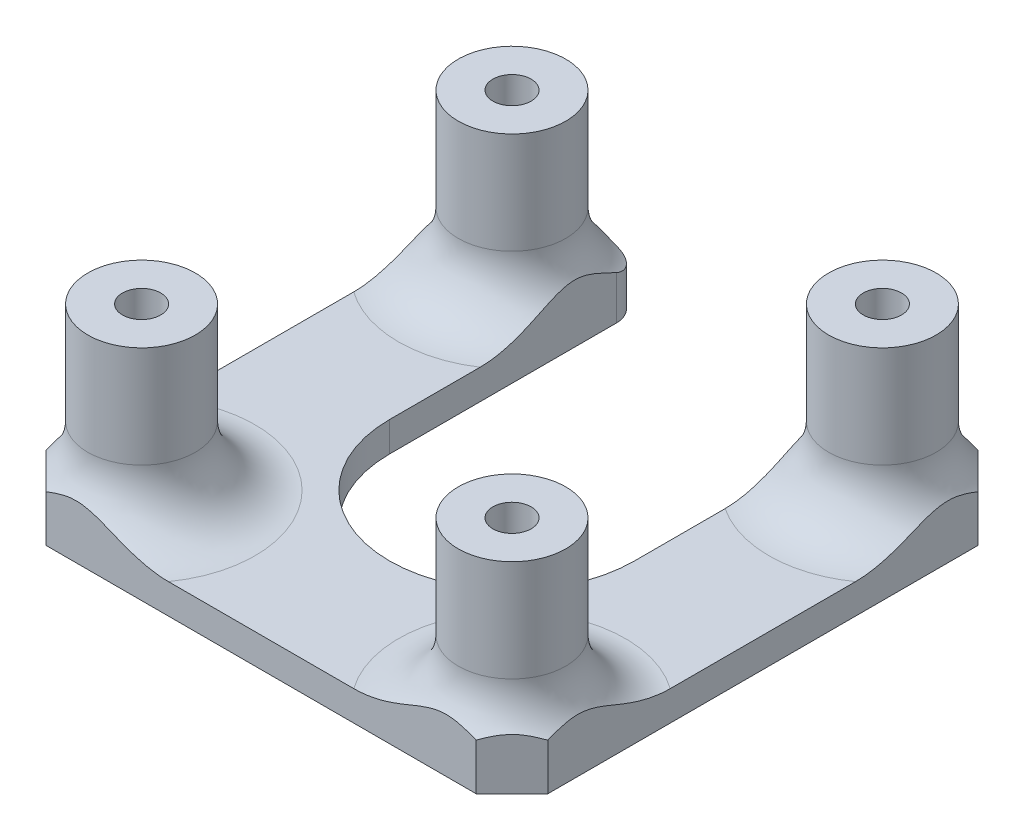
SolidWorks part; units mm, degrees
ref_plane "Alzado" through (0, 0, 0) normal (0, 0, 1) x (1, 0, 0)
ref_plane "Planta" through (0, 0, 0) normal (0, 1, 0) x (1, 0, 0)
ref_plane "Vista lateral" through (0, 0, 0) normal (1, 0, 0) x (0, 0, -1)
sketch "Croquis1" plane through (0, 0, 0) normal (0, 1, 0) x (1, 0, 0)
  line L0 (-10.25, 0) -> (-10.25, 21)
  line L1 (-21, -21) -> (21, -21)
  line L2 (-21, -21) -> (-21, 21)
  line L3 (-21, 21) -> (-10.25, 21)
  line L4 (21, -21) -> (21, 21)
  line L5 (-21, -21) -> (21, 21) construction
  line L6 (-21, 21) -> (21, -21) construction
  line L7 (-15.5, -15.5) -> (15.5, -15.5) construction
  line L8 (-15.5, -15.5) -> (-15.5, 15.5) construction
  line L9 (-15.5, 15.5) -> (15.5, 15.5) construction
  line L10 (15.5, -15.5) -> (15.5, 15.5) construction
  line L11 (-15.5, -15.5) -> (15.5, 15.5) construction
  line L12 (-15.5, 15.5) -> (15.5, -15.5) construction
  line L13 (10.25, 0) -> (10.25, 21)
  line L14 (10.25, 21) -> (21, 21)
  circle A0 centre (-15.5, 15.5) radius 1.6
  circle A1 centre (15.5, 15.5) radius 1.6
  circle A2 centre (15.5, -15.5) radius 1.6
  circle A3 centre (-15.5, -15.5) radius 1.6
  arc A4 (-10.25, 0) -> (10.25, 0) centre (0, 0) ccw
  point P0 (0, 0)
  point P6 (0, 0)
  dimension "D5" = 3.2
  dimension "D6" = 20.5
  dimension "D1" = 42
  dimension "D2" = 42
  dimension "D3" = 31
  dimension "D4" = 31
extrude "Saliente-Extruir1" add sketch "Croquis1" along normal blind 2.5
chamfer "Chaflán1" distance 3 angle 45 4 edges at (-21, 1.25, 21) (21, 1.25, 21) (-21, 1.25, -21) (21, 1.25, -21)
fillet "Redondeo1" radius 2 2 edges at (10.25, 1.25, -21) (-10.25, 1.25, -21)
sketch "Croquis2" plane through (0, 2.5, 0) normal (0, 1, 0) x (1, 0, 0)
  circle A0 centre (-15.5, 15.5) radius 4.5
  circle A1 centre (15.5, 15.5) radius 4.5
  circle A2 centre (15.5, -15.5) radius 4.5
  circle A3 centre (-15.5, -15.5) radius 4.5
  circle A4 centre (-15.5, -15.5) radius 1.6 construction
  circle A5 centre (15.5, -15.5) radius 1.6 construction
  circle A6 centre (15.5, 15.5) radius 1.6 construction
  circle A7 centre (-15.5, 15.5) radius 1.6 construction
  circle A8 centre (-15.5, -15.5) radius 1.6
  circle A9 centre (15.5, -15.5) radius 1.6
  circle A10 centre (15.5, 15.5) radius 1.6
  circle A11 centre (-15.5, 15.5) radius 1.6
  dimension "D1" = 9
extrude "Saliente-Extruir2" add sketch "Croquis2" along normal blind 13.5
fillet "Redondeo2" radius 5 4 edges at (-15.5, 2.5, 20) (15.5, 2.5, 20) (15.5, 2.5, -11) (-15.5, 2.5, -11)
